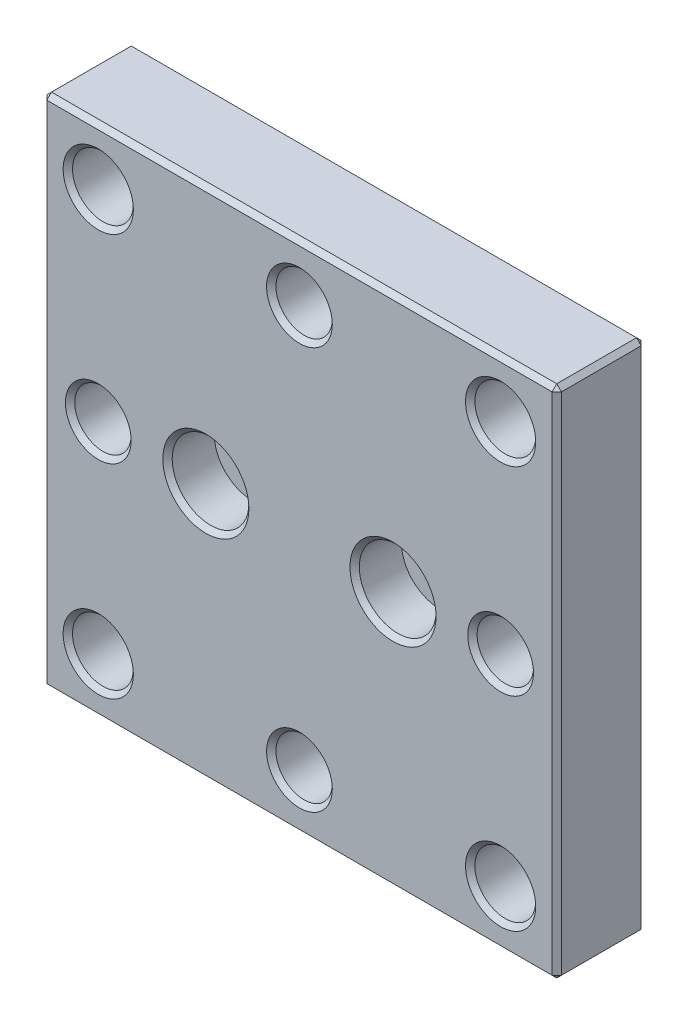
SolidWorks part; units mm, degrees
ref_plane "Front Plane" through (0, 0, 0) normal (0, 0, 1) x (1, 0, 0)
ref_plane "Top Plane" through (0, 0, 0) normal (0, 1, 0) x (1, 0, 0)
ref_plane "Right Plane" through (0, 0, 0) normal (1, 0, 0) x (0, 0, -1)
sketch "Sketch1" plane through (0, 0, 0) normal (0, 0, 1) x (1, 0, 0)
  line L1 (0, 0) -> (55, 0)
  line L2 (0, 0) -> (0, 55)
  line L3 (0, 55) -> (55, 55)
  line L4 (55, 0) -> (55, 55)
  circle A0 centre (27.5, 27.5) radius 15.125 construction
  circle A1 centre (17.5, 27.5) radius 2.2
  circle A2 centre (37.5, 27.5) radius 2.2
  circle A3 centre (17.5, 27.5) radius 4.1
  circle A4 centre (37.5, 27.5) radius 4.1
  dimension "D5" = 30.25
  dimension "D6" = 4.4
  dimension "D7" = 4.4
  dimension "D10" = 8.2
  dimension "D11" = 8.2
  dimension "D1" = 55
  dimension "D2" = 55
  dimension "D3" = 27.5
  dimension "D4" = 27.5
  dimension "D8" = 10
  dimension "D9" = 10
extrude "Boss-Extrude1" add sketch "Sketch1" along normal blind 9.525 contours L1 L4 L3 L2 A4 A3 region at (27.5, 27.5, 0)
extrude "Boss-Extrude2" add sketch "Sketch1<3>" along normal blind 4.525 contours A3 A1 | A4 A2 region at (13.516, 27.5, 0) region at (33.516, 27.5, 0)
sketch "Sketch1<3>" plane through (0, 0, 0) normal (0, 0, 1) x (1, 0, 0) same geometry as "Sketch1"
sketch "Sketch3" plane through (0, 0, 9.525) normal (0, 0, 1) x (1, 0, 0)
  line L0 (0, 55) -> (55, 55) construction
  line L1 (0, 0) -> (0, 55) construction
  line L2 (0, 0) -> (55, 0) construction
  line L3 (55, 0) -> (55, 55) construction
  circle A0 centre (27.5, 49) radius 3.0127
  circle A1 centre (6, 27.5) radius 3.0127
  circle A2 centre (49, 27.5) radius 3.0127
  circle A3 centre (27.5, 6) radius 3.0127
  dimension "D6" = 6.0254
  dimension "D7" = 6.0254
  dimension "D8" = 6.0254
  dimension "D9" = 6.0254
  dimension "D1" = 27.5
  dimension "D2" = 27.5
  dimension "D3" = 27.5
  dimension "D4" = 27.5
  dimension "D5" = 6
  dimension "D10" = 6
  dimension "D11" = 6
  dimension "D12" = 6
extrude "Cut-Extrude1" cut sketch "Sketch3" against normal through all
sketch "Sketch5" plane through (0, 0, 9.525) normal (0, 0, 1) x (1, 0, 0)
  line L0 (0, 55) -> (55, 55) construction
  line L1 (0, 0) -> (0, 55) construction
  circle A0 centre (6, 49) radius 3.2512
  circle A1 centre (49, 49) radius 3.2512
  circle A2 centre (49, 6) radius 3.2512
  circle A3 centre (6, 6) radius 3.2512
  dimension "D1" = 6.5024
  dimension "D2" = 6.5024
  dimension "D3" = 6.5024
  dimension "D4" = 6.5024
  dimension "D5" = 6
  dimension "D6" = 6
  dimension "D7" = 43
  dimension "D8" = 43
extrude "Cut-Extrude2" cut sketch "Sketch5" against normal blind 6.4008
chamfer "Chamfer1" distance 0.5 angle 45 28 edges at (52.0127, 27.5, 0) (39.7, 27.5, 0) (30.5127, 49, 0) (30.5127, 6, 0) (19.7, 27.5, 0) (9.0127, 27.5, 0) (9.2512, 49, 9.525) (9.2512, 6, 9.525) (9.0127, 27.5, 9.525) (21.6, 27.5, 9.525) (41.6, 27.5, 9.525) (30.5127, 6, 9.525) (52.2512, 6, 9.525) (52.0127, 27.5, 9.525) (52.2512, 49, 9.525) (30.5127, 49, 9.525) (27.5, 55, 0) (55, 55, 4.7625) (55, 27.5, 0) (55, 0, 4.7625) (27.5, 0, 0) (0, 27.5, 0) (0, 55, 4.7625) (0, 0, 4.7625) (55, 27.5, 9.525) (27.5, 0, 9.525) (0, 27.5, 9.525) (27.5, 55, 9.525)
sketch "Sketch6" plane through (0, 0, 9.525) normal (0, 0, 1) x (1, 0, 0)
  circle A0 centre (6, 49) radius 1.25
  circle A1 centre (49, 49) radius 1.25
  circle A2 centre (49, 6) radius 1.25
  circle A3 centre (6, 6) radius 1.25
  dimension "D1" = 2.5
  dimension "D2" = 2.5
  dimension "D3" = 2.5
  dimension "D4" = 2.5
extrude "Cut-Extrude3" cut sketch "Sketch6" against normal through all
chamfer "Chamfer2" distance 0.5 angle 45 8 edges at (7.25, 6, 3.1242) (50.25, 6, 3.1242) (50.25, 49, 3.1242) (7.25, 49, 3.1242) (7.25, 49, 0) (50.25, 49, 0) (50.25, 6, 0) (7.25, 6, 0)
